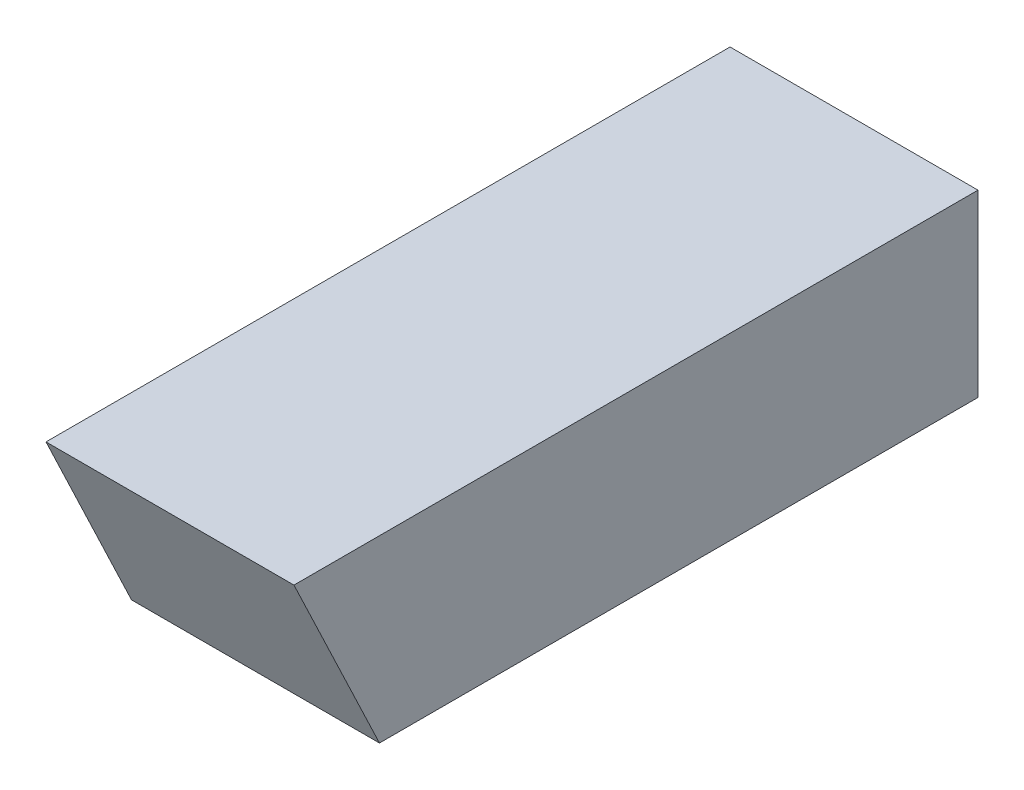
SolidWorks part; units mm, degrees
ref_plane "Front Plane" through (0, 0, 0) normal (0, 0, 1) x (1, 0, 0)
ref_plane "Top Plane" through (0, 0, 0) normal (0, 1, 0) x (1, 0, 0)
ref_plane "Right Plane" through (0, 0, 0) normal (1, 0, 0) x (0, 0, -1)
sketch "Sketch1" plane through (0, 0, 0) normal (1, 0, 0) x (0, 0, -1)
  line L0 (-350, 0) -> (0, 0)
  line L1 (0, 0) -> (0, 105)
  line L2 (0, 105) -> (-400, 105)
  line L3 (-400, 105) -> (-350, 0)
  point P5 (0, 0)
  dimension "D1" = 400
  dimension "D2" = 105
  dimension "D3" = 350
extrude "Boss-Extrude1" add sketch "Sketch1" along normal blind 145
hole_wizard "Tap Drill for 1/4-20 Tap1" positions "Sketch2" profile "Sketch3" hole size "1/4-20" standard "ANSI Inch"
sketch "Sketch2" plane through (0, 0, 0) normal (0, -1, 0) x (-1, 0, 0)
  line L0 (-72.5, -350) -> (-72.5, 0) construction
  line L1 (-145, -350) -> (0, -350) construction
  line L2 (-145, 0) -> (0, 0) construction
  point P0 (-72.5, -253)
  point P17 (-72.5, -203)
  point P18 (-72.5, -153)
  point P19 (0, 0)
  point P20 (0, 0)
  point P21 (-72.5, -192.0264)
  dimension "D1" = 97
  dimension "D3" = 50
  dimension "D2" = 3
sketch "Sketch3" plane through (72.5, 0, 253) normal (1, 0, 0) x (0, 0, -1)
  line L0 (0, 0) -> (0, 9.5338)
  line L1 (0, 9.5338) -> (2.5527, 8)
  line L2 (2.5527, 8) -> (2.5527, 0)
  line L5 (2.5527, 0) -> (0, 0)
  line L10 (0, 9.5338) -> (-2.5527, 8) construction
  line L11 (0, -6.35) -> (0, 107.95) construction
  dimension "Hole Dia." = 5.1054
  dimension "Hole Depth" = 8
  dimension "Drill Angle" = 118
sketch "Sketch4" plane through (0, 0, 0) normal (0, -1, 0) x (1, 0, 0)
  line L0 (72.5, 350) -> (72.5, 0) construction
  line L1 (45, 83) -> (100, 83)
  line L2 (45, 83) -> (45, 113)
  line L3 (45, 113) -> (100, 113)
  line L4 (100, 83) -> (100, 113)
  line L5 (45, 83) -> (100, 113) construction
  line L6 (45, 113) -> (100, 83) construction
  line L7 (145, 350) -> (0, 350) construction
  point P0 (72.5, 98)
  point P7 (0, 0)
  dimension "D1" = 30
  dimension "D2" = 55
  dimension "D3" = 237
extrude "Boss-Extrude2" add sketch "Sketch4" along normal blind 30
sketch "Sketch5" plane through (0, 0, 0) normal (0, -1, 0) x (1, 0, 0)
  line L0 (72.5, 288.5415) -> (608.0304, 1145.5693) construction
  line L1 (608.0304, 1145.5693) -> (-463.0304, 1145.5693) construction
  line L2 (-463.0304, 1145.5693) -> (72.5, 288.5415) construction
  line L3 (72.5, 350) -> (72.5, 1145.5693) construction
  line L4 (145, 350) -> (0, 350) construction
  dimension "D1" = 64
